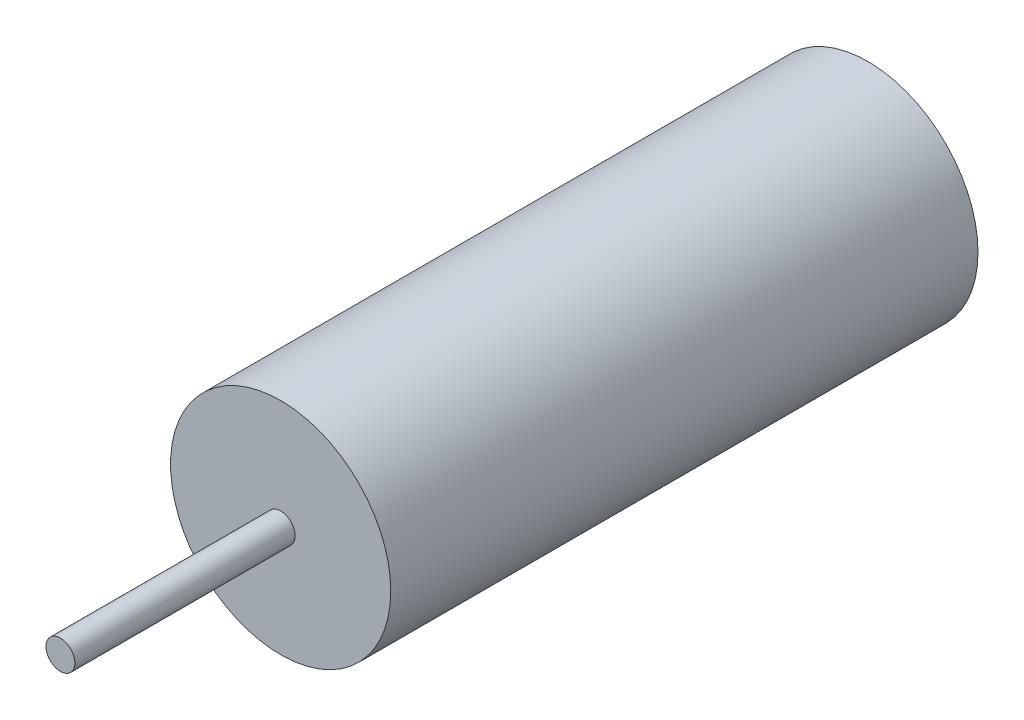
SolidWorks part; units mm, degrees
ref_plane "Front Plane" through (0, 0, 0) normal (0, 0, 1) x (1, 0, 0)
ref_plane "Top Plane" through (0, 0, 0) normal (0, 1, 0) x (1, 0, 0)
ref_plane "Right Plane" through (0, 0, 0) normal (1, 0, 0) x (0, 0, -1)
sketch "Sketch1" plane through (0, 0, 0) normal (0, 0, 1) x (1, 0, 0)
  circle A0 centre (0, 0) radius 19.05
  dimension "D1" = 38.1
extrude "Boss-Extrude1" add sketch "Sketch1" along normal blind 101.6
sketch "Sketch2" plane through (0, 0, 101.6) normal (0, 0, 1) x (1, 0, 0)
  circle A0 centre (0, 0) radius 2.5
  dimension "D1" = 5
extrude "Boss-Extrude2" add sketch "Sketch2" along normal blind 38.1
